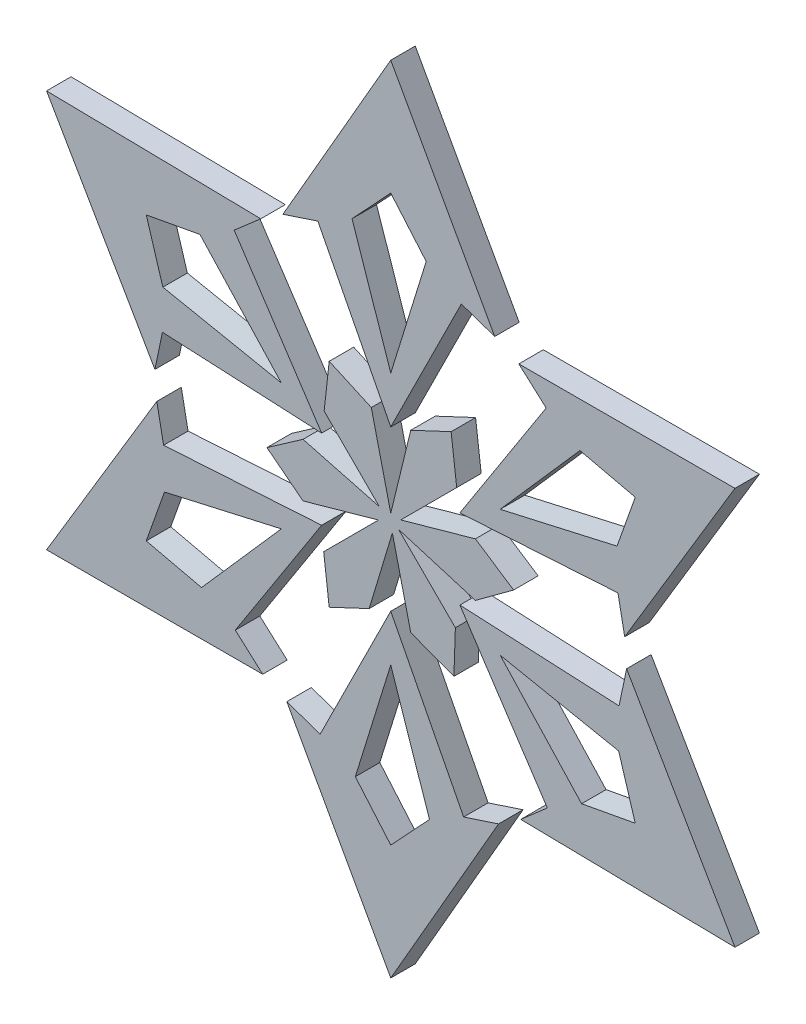
SolidWorks part; units mm, degrees
ref_plane "Спереди" through (0, 0, 0) normal (0, 0, 1) x (1, 0, 0)
ref_plane "Сверху" through (0, 0, 0) normal (0, 1, 0) x (1, 0, 0)
ref_plane "Справа" through (0, 0, 0) normal (1, 0, 0) x (0, 0, -1)
sketch "Эскиз2" plane through (0, 0, 0) normal (0, 0, 1) x (1, 0, 0)
  line L1 (-30, 30) -> (30, 30)
  line L2 (-30, 30) -> (-30, -30)
  line L3 (-30, -30) -> (30, -30)
  line L4 (30, 30) -> (30, -30)
  line L5 (-30, 30) -> (30, -30) construction
  line L6 (-30, -30) -> (30, 30) construction
  point P0 (0, 0)
  point P5 (0, 0)
  dimension "D1" = 60
  dimension "D2" = 60
extrude "Бобышка-Вытянуть1" add sketch "Эскиз2" along normal blind 1.5
sketch "Эскиз3" plane through (0, 0, 0) normal (0, 0, -1) x (-1, 0, 0)
  line L0 (0.7012, 0.3105) -> (4.0793, 3.6885)
  line L1 (4.0793, 3.6885) -> (3.7705, 6.4853)
  line L2 (3.7705, 6.4853) -> (1.1916, 5.323)
  line L3 (1.1916, 5.323) -> (0, 0.3105)
  line L4 (0, 0.3105) -> (-1.2239, 5.323)
  line L5 (-1.2239, 5.323) -> (-3.6978, 6.4853)
  line L6 (-3.6978, 6.4853) -> (-4.0389, 3.6885)
  line L7 (-4.0389, 3.6885) -> (-0.6119, 0.2616)
  line L8 (-0.6119, 0.2616) -> (-5.1837, 1.5428)
  line L9 (-5.1837, 1.5428) -> (-7.5259, 0)
  line L10 (-7.5259, 0) -> (-5.1837, -1.7236)
  line L11 (-5.1837, -1.7236) -> (-0.4792, -0.307)
  line L12 (-0.4792, -0.307) -> (-3.9571, -3.7849)
  line L13 (-3.9571, -3.7849) -> (-3.8683, -6.4092)
  line L14 (-3.8683, -6.4092) -> (-1.2239, -5.4104)
  line L15 (-1.2239, -5.4104) -> (-0.1007, -0.6856)
  line L16 (-0.1007, -0.6856) -> (1.322, -5.4104)
  line L17 (1.322, -5.4104) -> (3.7705, -6.5607)
  line L18 (3.7705, -6.5607) -> (4.109, -3.7849)
  line L19 (4.109, -3.7849) -> (0.7527, -0.4286)
  line L20 (0.7527, -0.4286) -> (5.3736, -1.7236)
  line L21 (5.3736, -1.7236) -> (7.5844, 0)
  line L22 (7.5844, 0) -> (5.3736, 1.5428)
  line L23 (5.3736, 1.5428) -> (0.7012, 0.3105)
  line L25 (0, 4.8883) -> (-4.3238, 13.5699)
  line L26 (-4.3238, 13.5699) -> (-6.3663, 12.8678)
  line L27 (-6.3663, 12.8678) -> (0, 24.3421)
  line L29 (0, 24.3421) -> (6.6024, 12.8678)
  line L30 (6.6024, 12.8678) -> (4.464, 13.5699)
  line L34 (-2.171, 14.7496) -> (0, 17.2915)
  line L35 (0, 17.2915) -> (2.3703, 14.7496)
  line L36 (2.3703, 14.7496) -> (0, 7.7403)
  line L37 (0, 7.7403) -> (-2.171, 14.7496)
  line L38 (0, 4.8883) -> (4.464, 13.5699)
  line L39 (4.2334, 2.4441) -> (9.5899, 10.5295)
  line L40 (9.5899, 10.5295) -> (7.9607, 11.9473)
  line L41 (7.9607, 11.9473) -> (21.0808, 12.171)
  line L42 (21.0808, 12.171) -> (14.445, 0.716)
  line L43 (14.445, 0.716) -> (13.9838, 2.919)
  line L44 (11.688, 9.2549) -> (14.9749, 8.6457)
  line L45 (14.9749, 8.6457) -> (13.9587, 5.322)
  line L46 (13.9587, 5.322) -> (6.7033, 3.8701)
  line L47 (6.7033, 3.8701) -> (11.688, 9.2549)
  line L48 (4.2334, 2.4441) -> (13.9838, 2.919)
  line L49 (4.2334, -2.4441) -> (13.9138, -3.0404)
  line L50 (13.9138, -3.0404) -> (14.327, -0.9205)
  line L51 (14.327, -0.9205) -> (21.0808, -12.171)
  line L52 (21.0808, -12.171) -> (7.8426, -12.1517)
  line L53 (7.8426, -12.1517) -> (9.5199, -10.6509)
  line L54 (13.859, -5.4947) -> (14.9749, -8.6457)
  line L55 (14.9749, -8.6457) -> (11.5884, -9.4276)
  line L56 (11.5884, -9.4276) -> (6.7033, -3.8701)
  line L57 (6.7033, -3.8701) -> (13.859, -5.4947)
  line L58 (4.2334, -2.4441) -> (9.5199, -10.6509)
  line L59 (0, -4.8883) -> (4.3238, -13.5699)
  line L60 (4.3238, -13.5699) -> (6.3663, -12.8678)
  line L61 (6.3663, -12.8678) -> (0, -24.3421)
  line L62 (0, -24.3421) -> (-6.6024, -12.8678)
  line L63 (-6.6024, -12.8678) -> (-4.464, -13.5699)
  line L64 (2.171, -14.7496) -> (0, -17.2915)
  line L65 (0, -17.2915) -> (-2.3703, -14.7496)
  line L66 (-2.3703, -14.7496) -> (0, -7.7403)
  line L67 (0, -7.7403) -> (2.171, -14.7496)
  line L68 (0, -4.8883) -> (-4.464, -13.5699)
  line L69 (-4.2334, -2.4441) -> (-9.5899, -10.5295)
  line L70 (-9.5899, -10.5295) -> (-7.9607, -11.9473)
  line L71 (-7.9607, -11.9473) -> (-21.0808, -12.171)
  line L72 (-21.0808, -12.171) -> (-14.445, -0.716)
  line L73 (-14.445, -0.716) -> (-13.9838, -2.919)
  line L74 (-11.688, -9.2549) -> (-14.9749, -8.6457)
  line L75 (-14.9749, -8.6457) -> (-13.9587, -5.322)
  line L76 (-13.9587, -5.322) -> (-6.7033, -3.8701)
  line L77 (-6.7033, -3.8701) -> (-11.688, -9.2549)
  line L78 (-4.2334, -2.4441) -> (-13.9838, -2.919)
  line L79 (-4.2334, 2.4441) -> (-13.9138, 3.0404)
  line L80 (-13.9138, 3.0404) -> (-14.327, 0.9205)
  line L81 (-14.327, 0.9205) -> (-21.0808, 12.171)
  line L82 (-21.0808, 12.171) -> (-7.8426, 12.1517)
  line L83 (-7.8426, 12.1517) -> (-9.5199, 10.6509)
  line L84 (-13.859, 5.4947) -> (-14.9749, 8.6457)
  line L85 (-14.9749, 8.6457) -> (-11.5884, 9.4276)
  line L86 (-11.5884, 9.4276) -> (-6.7033, 3.8701)
  line L87 (-6.7033, 3.8701) -> (-13.859, 5.4947)
  line L88 (-4.2334, 2.4441) -> (-9.5199, 10.6509)
  point P86 (0, 0)
  dimension "D1" = 6
extrude "Вырез-Вытянуть1" cut sketch "Эскиз3" against normal blind 1.5 flip side to cut
